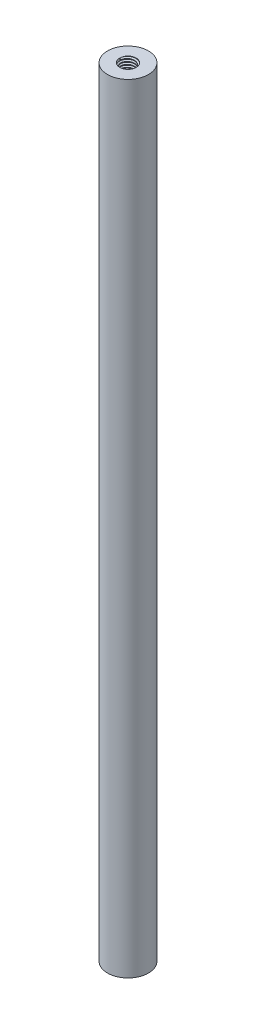
SolidWorks part; units mm, degrees
material "1060 Alloy"
ref_plane "Front Plane" through (0, 0, 0) normal (0, 0, 1) x (1, 0, 0)
ref_plane "Top Plane" through (0, 0, 0) normal (0, 1, 0) x (1, 0, 0)
ref_plane "Right Plane" through (0, 0, 0) normal (1, 0, 0) x (0, 0, -1)
sketch "Sketch1" plane through (0, 0, 0) normal (0, 1, 0) x (1, 0, 0)
  circle A0 centre (0, 0) radius 10
  dimension "D1" = 20
extrude "Boss-Extrude1" add sketch "Sketch1" along normal blind 190
hole_wizard "Ø8.0mm Dowel Hole1" positions "Sketch2" profile "Sketch4" hole size "Ø8.0" standard "BSI"
sketch "Sketch2" plane through (0, 190, 0) normal (0, 1, 0) x (1, 0, 0)
  point P0 (0, 0)
sketch "Sketch4" plane through (0, 190, 0) normal (1, 0, 0) x (0, 0, 1)
  line L0 (0, 0) -> (0, 22.4034)
  line L1 (0, 22.4034) -> (4, 20)
  line L2 (4, 20) -> (4, 0)
  line L5 (4, 0) -> (0, 0)
  line L10 (0, 22.4034) -> (-4, 20) construction
  line L11 (0, -6.35) -> (0, 107.95) construction
  dimension "Hole Dia." = 8
  dimension "Hole Depth" = 20
  dimension "Drill Angle" = 118
thread "Thread1" pitch 1.25 method extrude profile "Thread Profile1" start angle 0, offset 0, length 20, pitch 1.25, diameter 8
ref_plane "Plane1" through (-4, 190, 0) normal (0, 0, 1) x (-1, 0, 0)
sketch "Thread Profile1" plane through (-4, 190, 0) normal (0, 0, 1) x (-1, 0, 0)
  line L0 (0, 0) -> (0, 1.25) construction
  line L11 (0, 0) -> (0, 1.0937)
  line L12 (0, 1.0937) -> (-0.6766, 0.7031)
  line L13 (-0.6766, 0.7031) -> (-0.6766, 0.3906)
  line L15 (-0.6766, 0.3906) -> (0, 0)
  line L17 (-0.6766, 0.5469) -> (0, 0.5469) construction
  point P2 (0, 0)
  dimension "Pitch" = 1.25
  dimension "Profile_Angle" = 60
  dimension "Profile_Land" = 0.3125
  dimension "Profile_Height" = 0.6766
mirror "Mirror2" about plane through (0, 0, 0) normal (0, 1, 0) of "Ø8.0mm Dowel Hole1", "Boss-Extrude1"
thread "Thread2" pitch 1.25 method extrude profile "Thread Profile2" start angle 0, offset 0, length 20, pitch 1.25, diameter 8
ref_plane "Plane2" through (4, -190, 0) normal (0, 0, 1) x (1, 0, 0)
sketch "Thread Profile2" plane through (4, -190, 0) normal (0, 0, 1) x (1, 0, 0)
  line L0 (0, 0) -> (0, 1.25) construction
  line L11 (0, 0) -> (0, 1.0937)
  line L12 (0, 1.0937) -> (-0.6766, 0.7031)
  line L13 (-0.6766, 0.7031) -> (-0.6766, 0.3906)
  line L15 (-0.6766, 0.3906) -> (0, 0)
  line L17 (-0.6766, 0.5469) -> (0, 0.5469) construction
  point P2 (0, 0)
  dimension "Pitch" = 1.25
  dimension "Profile_Angle" = 60
  dimension "Profile_Land" = 0.3125
  dimension "Profile_Height" = 0.6766
